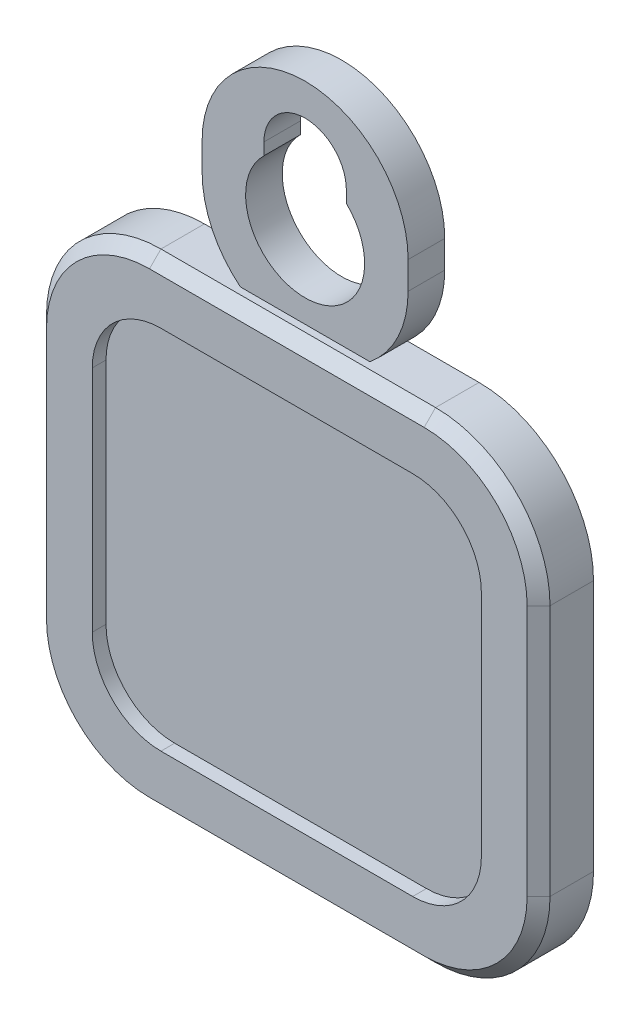
SolidWorks part; units mm, degrees
ref_plane "Front Plane" through (0, 0, 0) normal (0, 0, 1) x (1, 0, 0)
ref_plane "Top Plane" through (0, 0, 0) normal (0, 1, 0) x (1, 0, 0)
ref_plane "Right Plane" through (0, 0, 0) normal (1, 0, 0) x (0, 0, -1)
sketch "Sketch1" plane through (0, 0, 0) normal (0, 0, 1) x (1, 0, 0)
  line L0 (-6, 29) -> (6, 29)
  line L1 (11, 34) -> (11, 45)
  line L2 (6, 50) -> (-6, 50)
  line L3 (-11, 45) -> (-11, 34)
  arc A0 (-11, 34) -> (-6, 29) centre (-6, 34) ccw
  arc A1 (6, 29) -> (11, 34) centre (6, 34) ccw
  arc A2 (11, 45) -> (6, 50) centre (6, 45) ccw
  arc A3 (-6, 50) -> (-11, 45) centre (-6, 45) ccw
extrude "Boss-Extrude1" add sketch "Sketch1" along normal blind 2.4 from offset 80.3
sketch "Sketch2" plane through (0, 0, 0) normal (0, 0, 1) x (1, 0, 0)
  line L0 (4.5, 53.5) -> (4.5, 54.7)
  line L1 (-4.5, 54.7) -> (-4.5, 53.5)
  arc A0 (-4.5, 53.5) -> (0, 49) centre (0, 53.5) ccw
  arc A1 (0, 49) -> (4.5, 53.5) centre (0, 53.5) ccw
  arc A2 (4.5, 54.7) -> (0, 59.2) centre (0, 54.7) ccw
  arc A3 (0, 59.2) -> (-4.5, 54.7) centre (0, 54.7) ccw
extrude "Boss-Extrude2" add sketch "Sketch2" along normal blind 1.6 from offset 80.3
sketch "Sketch3" plane through (0, 0, 0) normal (0, 0, 1) x (1, 0, 0)
  line L0 (-1.8, 56) -> (-1.8, 53.6)
  line L1 (1.8, 53.6) -> (1.8, 56)
  arc A0 (-1.8, 53.6) -> (1.8, 53.6) centre (0, 53.6) ccw
  arc A1 (1.8, 56) -> (-1.8, 56) centre (0, 56) ccw
extrude "Boss-Extrude3" add sketch "Sketch3" along normal blind 4.4 from offset 79.3 separate body
combine bodies "Combine1" operation type subtract main body 102 bodies to subtract 103
sketch "Sketch4" plane through (0, 0, 0) normal (0, 0, 1) x (1, 0, 0)
  circle A0 centre (0, 53.6) radius 2.6
extrude "Boss-Extrude4" add sketch "Sketch4" along normal blind 4.4 from offset 79.3 separate body
combine bodies "Combine2" operation type subtract main body 104 bodies to subtract 105
sketch "Sketch5" plane through (0, 0, 0) normal (0, 0, 1) x (1, 0, 0)
  line L0 (-5.5, 31.5) -> (5.5, 31.5)
  line L1 (8.5, 34.5) -> (8.5, 44.5)
  line L2 (5.5, 47.5) -> (-5.5, 47.5)
  line L3 (-8.5, 44.5) -> (-8.5, 34.5)
  arc A0 (-8.5, 34.5) -> (-5.5, 31.5) centre (-5.5, 34.5) ccw
  arc A1 (5.5, 31.5) -> (8.5, 34.5) centre (5.5, 34.5) ccw
  arc A2 (8.5, 44.5) -> (5.5, 47.5) centre (5.5, 44.5) ccw
  arc A3 (-5.5, 47.5) -> (-8.5, 44.5) centre (-5.5, 44.5) ccw
extrude "Boss-Extrude5" add sketch "Sketch5" along normal blind 1.6 from offset 82.1 separate body
combine bodies "Combine3" operation type subtract main body 106 bodies to subtract 107
chamfer "Chamfer1" distance 0.5 angle 45 8 edges at (0, 50, 82.7) (-9.5355, 48.5355, 82.7) (9.5355, 48.5355, 82.7) (-11, 39.5, 82.7) (11, 39.5, 82.7) (-9.5355, 30.4645, 82.7) (9.5355, 30.4645, 82.7) (0, 29, 82.7)
